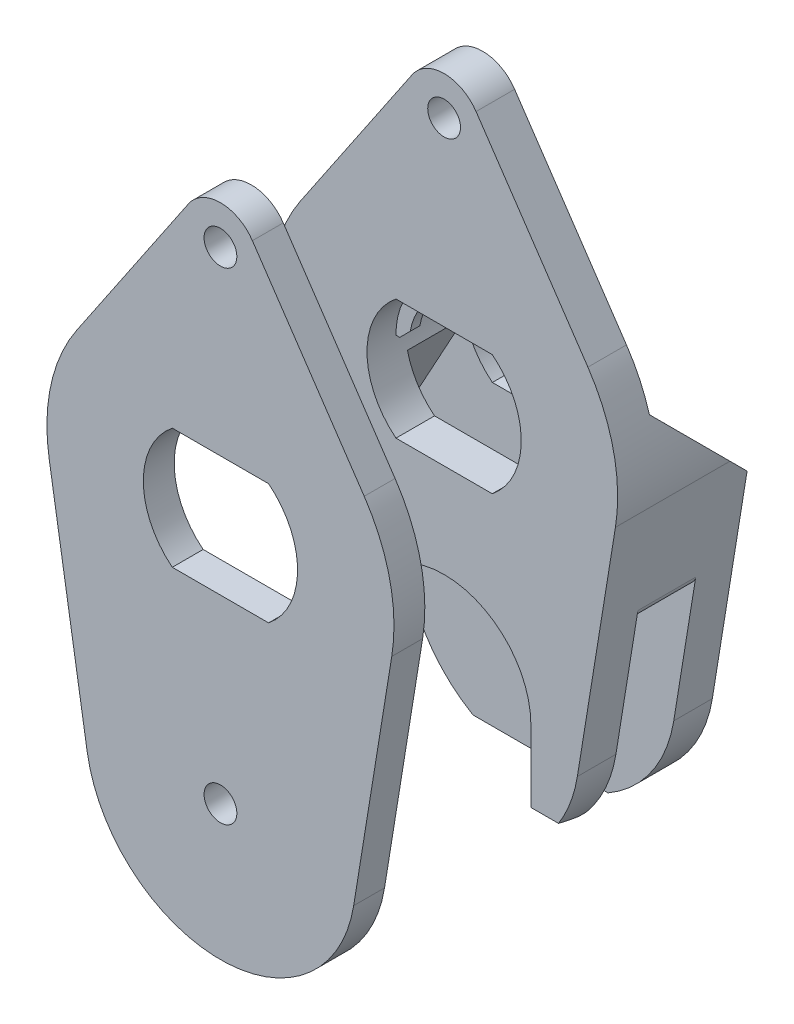
SolidWorks part; units mm, degrees
ref_plane "Front Plane" through (0, 0, 0) normal (0, 0, 1) x (1, 0, 0)
ref_plane "Top Plane" through (0, 0, 0) normal (0, 1, 0) x (1, 0, 0)
ref_plane "Right Plane" through (0, 0, 0) normal (1, 0, 0) x (0, 0, -1)
sketch "Sketch1" plane through (0, 0, 0) normal (0, 0, 1) x (1, 0, 0)
  line L0 (-14.9129, 10.08) -> (-3.314, 27.24)
  line L1 (3.314, 27.24) -> (14.9129, 10.08)
  line L2 (0, 25) -> (0, -25) construction
  line L3 (-17.7681, -2.88) -> (-13.8196, -27.24)
  line L4 (-4.9937, -6.25) -> (4.9937, -6.25)
  line L5 (4.9937, 6.25) -> (-4.9937, 6.25)
  line L6 (17.7681, -2.88) -> (13.8196, -27.24)
  arc A0 (-14.9129, 10.08) -> (-17.7681, -2.88) centre (0, 0) ccw
  arc A1 (-3.314, 27.24) -> (3.314, 27.24) centre (0, 25) cw
  circle A2 centre (0, -25) radius 1.7
  arc A3 (-13.8196, -27.24) -> (13.8196, -27.24) centre (0, -25) ccw
  arc A4 (-4.9937, 6.25) -> (-4.9937, -6.25) centre (0, 0) ccw
  arc A5 (4.9937, -6.25) -> (4.9937, 6.25) centre (0, 0) ccw
  circle A6 centre (0, 25) radius 1.7
  arc A7 (17.7681, -2.88) -> (14.9129, 10.08) centre (0, 0) ccw
  dimension "D2" = 36
  dimension "D3" = 3.4
  dimension "D5" = 4
  dimension "D1" = 8
  dimension "D7" = 28
  dimension "D4" = 25
  dimension "D6" = 12.5
extrude "Boss-Extrude1" add sketch "Sketch1" against normal blind 3.2
sketch "Sketch2" plane through (0, 0, -3.2) normal (0, 0, -1) x (-1, 0, 0)
  line L4 (4.9937, -6.25) -> (-4.9937, -6.25) construction
  line L5 (-4.9937, 6.25) -> (4.9937, 6.25) construction
  line L6 (4.9937, -6.25) -> (-4.9937, -6.25)
  line L7 (-4.9937, 6.25) -> (4.9937, 6.25)
  line L8 (14.9129, 10.08) -> (3.314, 27.24)
  line L9 (-3.314, 27.24) -> (-14.9129, 10.08)
  line L10 (-17.7681, -2.88) -> (-13.8196, -27.24)
  line L11 (13.8196, -27.24) -> (17.7681, -2.88)
  line L12 (14.9129, 10.08) -> (3.314, 27.24)
  line L13 (-3.314, 27.24) -> (-14.9129, 10.08)
  line L14 (-17.7681, -2.88) -> (-13.8196, -27.24)
  line L15 (13.8196, -27.24) -> (17.7681, -2.88)
  circle A4 centre (0, 25) radius 1.7 construction
  circle A5 centre (0, -25) radius 1.7 construction
  arc A6 (4.9937, -6.25) -> (4.9937, 6.25) centre (0, 0) ccw construction
  arc A7 (-4.9937, 6.25) -> (-4.9937, -6.25) centre (0, 0) ccw construction
  arc A8 (17.7681, -2.88) -> (14.9129, 10.08) centre (0, 0) ccw
  arc A9 (3.314, 27.24) -> (-3.314, 27.24) centre (0, 25) ccw
  arc A10 (-14.9129, 10.08) -> (-17.7681, -2.88) centre (0, 0) ccw
  arc A11 (-13.8196, -27.24) -> (13.8196, -27.24) centre (0, -25) ccw
  arc A12 (17.7681, -2.88) -> (14.9129, 10.08) centre (0, 0) ccw
  arc A13 (3.314, 27.24) -> (-3.314, 27.24) centre (0, 25) ccw
  arc A14 (-14.9129, 10.08) -> (-17.7681, -2.88) centre (0, 0) ccw
  arc A15 (-13.8196, -27.24) -> (13.8196, -27.24) centre (0, -25) ccw
  circle A16 centre (0, 25) radius 1.7
  circle A17 centre (0, -25) radius 1.7
  arc A18 (4.9937, -6.25) -> (4.9937, 6.25) centre (0, 0) ccw
  arc A19 (-4.9937, 6.25) -> (-4.9937, -6.25) centre (0, 0) ccw
  dimension "D1" = 0
extrude "Boss-Extrude2" add sketch "Sketch2" along normal blind 14 from offset 20 separate body
sketch "Sketch3" plane through (0, 0, -23.2) normal (0, 0, 1) x (1, 0, 0)
  line L0 (0, -25) -> (0, -39) construction
  line L1 (9, -25) -> (9, -39)
  line L2 (-9, -25) -> (-9, -39)
  arc A0 (9, -25) -> (-9, -25) centre (0, -25) ccw
  arc A1 (-9, -39) -> (9, -39) centre (0, -39) ccw
  arc A2 (-13.8196, -27.24) -> (13.8196, -27.24) centre (0, -25) ccw construction
  point P2 (0, -32)
  point P8 (0, -25)
  point P9 (0, -39)
  dimension "D1" = 18
extrude "Cut-Extrude1" cut sketch "Sketch3" against normal blind 10
sketch "Sketch4" plane through (0, 0, -33.2) normal (0, 0, 1) x (1, 0, 0)
  circle A0 centre (0, -25) radius 17
  dimension "D1" = 34
extrude "Cut-Extrude2" cut sketch "Sketch4" along normal blind 6
sketch "Sketch5" plane through (0, 0, -37.2) normal (0, 0, -1) x (-1, 0, 0)
  line L0 (-12.2818, -18.28) -> (-1.7545, 0.96) construction
  line L1 (1.7545, 0.96) -> (12.2818, -18.28) construction
  line L2 (-15.7908, -16.36) -> (-5.2636, 2.88)
  line L3 (5.2636, 2.88) -> (15.7908, -16.36)
  arc A0 (1.7545, 0.96) -> (-1.7545, 0.96) centre (0, 0) ccw construction
  arc A1 (-12.2818, -18.28) -> (12.2818, -18.28) centre (0, -25) ccw construction
  arc A2 (5.2636, 2.88) -> (-5.2636, 2.88) centre (0, 0) ccw
  arc A3 (-15.7908, -16.36) -> (15.7908, -16.36) centre (0, -25) ccw
  dimension "D1" = 28
  dimension "D2" = 4
  dimension "D3" = 4
extrude "Cut-Extrude3" cut sketch "Sketch5" against normal up to surface (10 mm away) from vertex up to face at (0, -24.1894, -27.2) starting at point (15.3626, -17.7206, -33.2)
fillet "Fillet1" radius 1 4 edges at (15.6306, -16.0672, -30.2) (-15.6306, -16.0672, -30.2) (-9, -35.7238, -25.2) (9, -35.7238, -25.2)
sketch "Sketch6" plane through (0, 0, -37.2) normal (0, 0, -1) x (-1, 0, 0)
  line L0 (-8, 0) -> (-18, 0)
  line L1 (8, 0) -> (18, 0)
  line L2 (4.9937, 6.25) -> (-4.9937, 6.25) construction
  line L3 (4.9937, 6.25) -> (-4.9937, 6.25)
  line L4 (14.9129, 10.08) -> (3.314, 27.24) construction
  line L5 (-3.314, 27.24) -> (-14.9129, 10.08) construction
  line L6 (14.9129, 10.08) -> (3.314, 27.24)
  line L7 (-3.314, 27.24) -> (-14.9129, 10.08)
  arc A0 (-4.9937, 6.25) -> (-4.9937, -6.25) centre (0, 0) ccw construction
  arc A1 (-14.9129, 10.08) -> (-17.7681, -2.88) centre (0, 0) ccw construction
  arc A2 (4.9937, -6.25) -> (4.9937, 6.25) centre (0, 0) ccw construction
  arc A3 (17.7681, -2.88) -> (14.9129, 10.08) centre (0, 0) ccw construction
  arc A4 (8, 0) -> (4.9937, 6.25) centre (0, 0) ccw
  arc A5 (-4.9937, 6.25) -> (-8, 0) centre (0, 0) ccw
  arc A6 (3.314, 27.24) -> (-3.314, 27.24) centre (0, 25) ccw construction
  arc A7 (18, 0) -> (14.9129, 10.08) centre (0, 0) ccw
  arc A8 (3.314, 27.24) -> (-3.314, 27.24) centre (0, 25) ccw
  arc A9 (-14.9129, 10.08) -> (-18, 0) centre (0, 0) ccw
extrude "Cut-Extrude4" cut sketch "Sketch6" against normal up to surface (10 mm away) up to face at (0, -18.9297, -27.2)
sketch "Sketch7" plane through (0, 0, -27.2) normal (0, 0, -1) x (-1, 0, 0)
  line L0 (-4.9937, 6.25) -> (4.9937, 6.25) construction
  line L1 (-4.9937, 6.25) -> (4.9937, 6.25)
  line L2 (-4.4763, 4.85) -> (4.4763, 4.85)
  line L3 (-8, 0) -> (-6.6, 0)
  line L4 (6.6, 0) -> (8, 0)
  arc A0 (8, 0) -> (4.9937, 6.25) centre (0, 0) ccw construction
  arc A1 (-4.9937, 6.25) -> (-8, 0) centre (0, 0) ccw construction
  arc A2 (8, 0) -> (4.9937, 6.25) centre (0, 0) ccw
  arc A3 (-4.9937, 6.25) -> (-8, 0) centre (0, 0) ccw
  arc A4 (6.6, 0) -> (4.4763, 4.85) centre (0, 0) ccw
  arc A5 (-4.4763, 4.85) -> (-6.6, 0) centre (0, 0) ccw
  arc A6 (-4.4763, 4.85) -> (-6.6, 0) centre (0, 0) ccw construction
  dimension "D1" = 1.4
extrude "Boss-Extrude3" add sketch "Sketch7" against normal blind 1
chamfer "Chamfer1" distance 1 angle 45 2 edges at (-6.6, 0, -26.7) (6.6, 0, -26.7)
chamfer "Chamfer2" distance 5 angle 45 4 edges at (13, 0, -37.2) (-13, 0, -37.2) (-13, 0, -27.2) (13, 0, -27.2)
sketch "Sketch9" plane through (0, 0, 0) normal (1, 0, 0) x (0, 0, -1)
  line L0 (37.2, -39) -> (23.2, -32.4293)
  line L1 (23.2, -32.4293) -> (23.2, -39)
  line L2 (23.2, -39) -> (37.2, -39)
  line L3 (23.2, -27.24) -> (23.2, -33.9456) construction
  point P8 (27.2, -34.3066)
extrude "Cut-Extrude5" cut sketch "Sketch9" against normal through all both and the other way through all
